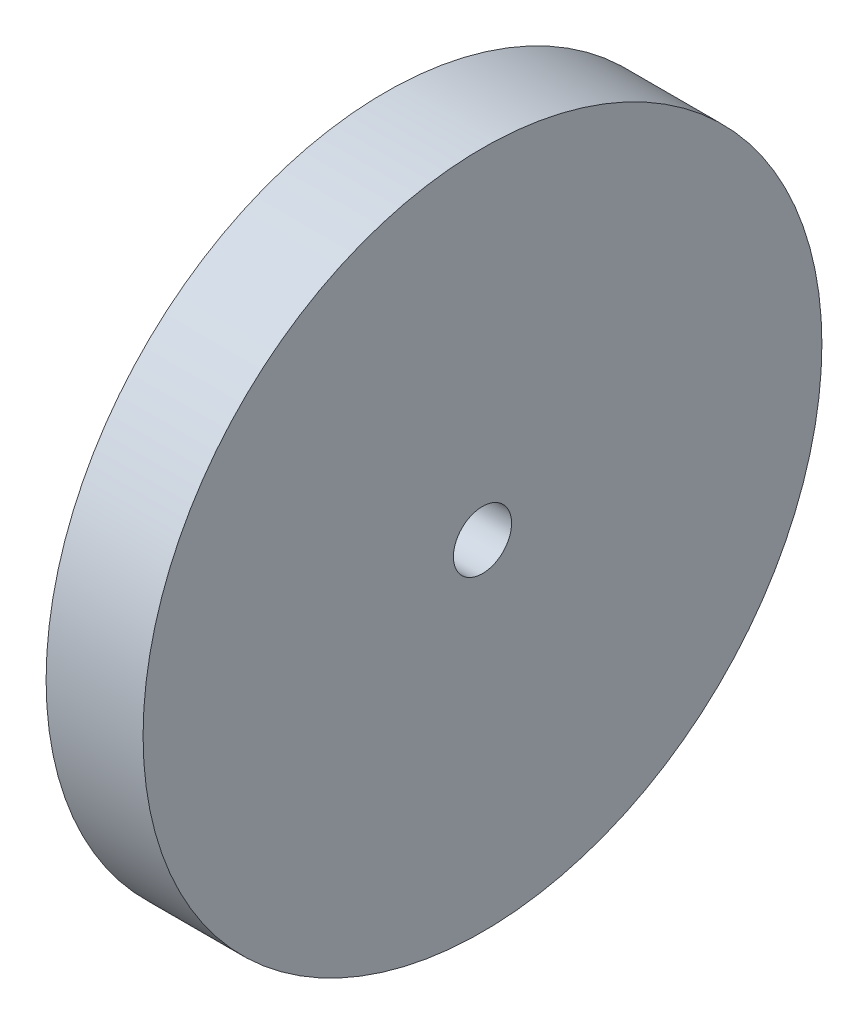
SolidWorks part; units mm, degrees
material "Nylon 101"
ref_plane "Front Plane" through (0, 0, 0) normal (0, 0, 1) x (1, 0, 0)
ref_plane "Top Plane" through (0, 0, 0) normal (0, 1, 0) x (1, 0, 0)
ref_plane "Right Plane" through (0, 0, 0) normal (1, 0, 0) x (0, 0, -1)
sketch "Sketch1" plane through (0, 0, 0) normal (1, 0, 0) x (0, 0, -1)
  circle A0 centre (0, 0) radius 3
  circle A1 centre (0, 0) radius 35
extrude "Boss-Extrude1" add sketch "Sketch1" along normal blind 10
